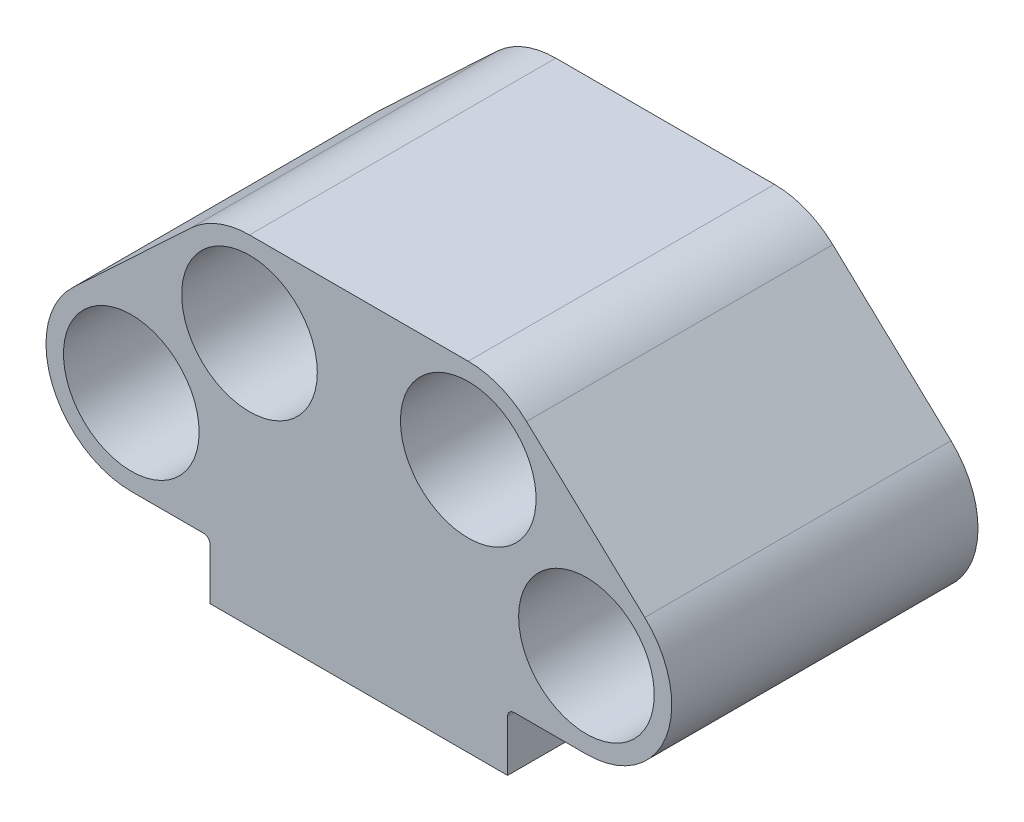
SolidWorks part; units mm, degrees
ref_plane "Front Plane" through (0, 0, 0) normal (0, 0, 1) x (1, 0, 0)
ref_plane "Top Plane" through (0, 0, 0) normal (0, 1, 0) x (1, 0, 0)
ref_plane "Right Plane" through (0, 0, 0) normal (1, 0, 0) x (0, 0, -1)
sketch "Sketch1" plane through (0, 0, 0) normal (0, 0, 1) x (1, 0, 0)
  line L0 (-11.9595, 12.7758) -> (-50.7466, -23.5332) construction
  line L1 (11.9595, 12.7758) -> (50.7466, -23.5332) construction
  line L2 (-11.9595, 12.7758) -> (11.9595, 12.7758) construction
  line L3 (-50.7466, -23.5332) -> (50.7466, -23.5332) construction
  line L4 (-17.5, -2) -> (17.5, -2) construction
  line L5 (0, 0) -> (0, -2) construction
  line L6 (-17.5, -2) -> (-17.5, 4) construction
  line L7 (-17.5, 4) -> (-20.5, 4) construction
  line L8 (-20.5, 4) -> (-20.5, -5) construction
  line L9 (-20.5, -5) -> (20.5, -5) construction
  line L10 (20.5, -5) -> (20.5, 4) construction
  line L11 (20.5, 4) -> (17.5, 4) construction
  line L12 (17.5, 4) -> (17.5, -2) construction
  line L13 (0, -2) -> (0, 40.1846) construction
  line L14 (-26.0058, 14.352) -> (-12.5, 26.995) construction
  line L15 (-32.669, 21.47) -> (-19.1632, 34.1129)
  line L16 (-26.0058, 4.602) -> (-17.75, 4.602)
  line L17 (-17, 3.852) -> (-17, -2)
  line L18 (-17, -2) -> (0, -2)
  line L19 (-12.5, 36.745) -> (0, 36.745)
  line L20 (0, 36.745) -> (0, -2)
  circle A0 centre (0, 0) radius 17.5 construction
  circle A1 centre (-26.0058, 14.352) radius 7.75
  circle A2 centre (-12.5, 26.995) radius 7.75
  circle A3 centre (-12.5, 26.995) radius 9.75 construction
  circle A4 centre (-26.0058, 14.352) radius 9.75 construction
  arc A5 (-17.75, 4.602) -> (-17, 3.852) centre (-17.75, 3.852) cw
  arc A6 (-19.1632, 34.1129) -> (-12.5, 36.745) centre (-12.5, 26.995) cw
  arc A7 (-26.0058, 4.602) -> (-32.669, 21.47) centre (-26.0058, 14.352) cw
  dimension "D1" = 35
  dimension "D8" = 15.5
  dimension "D10" = 3
  dimension "D11" = 2
  dimension "D13" = 0.75
  dimension "D2" = 93.78
  dimension "D3" = 35
  dimension "2" = 2
  dimension "D4" = 6
  dimension "D5" = 3
  dimension "D6" = 3
  dimension "D7" = 3
  dimension "D9" = 25
  dimension "D12" = 0.5
extrude "Boss-Extrude1" add sketch "Sketch1" along normal mid plane 35 contours A7 L16 A5 L17 L18 L20 L19 A6 L15 A2 A1 region at (-12.1141, 15.2891, 0)
mirror "Mirror1" about plane through (0, 0, 0) normal (1, 0, 0) of "Boss-Extrude1"
